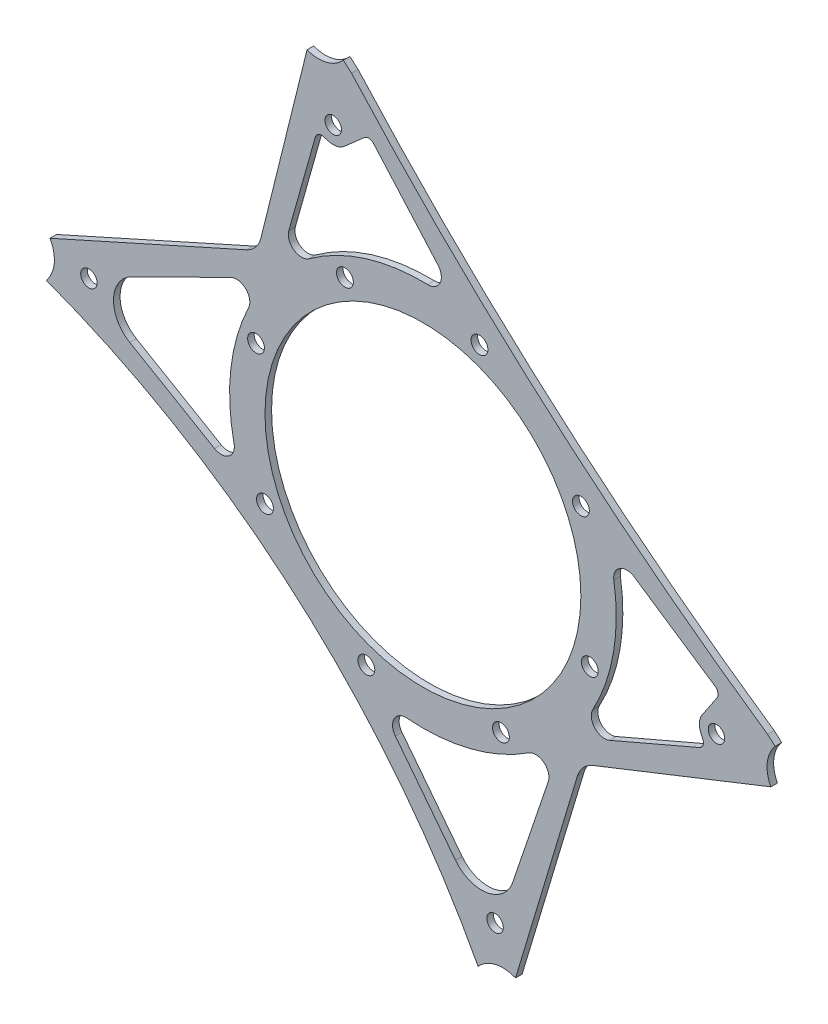
SolidWorks part; units mm, degrees
material "AISI 4130 Steel, normalized at 870C"
ref_plane "Front Plane" through (0, 0, 0) normal (0, 0, 1) x (1, 0, 0)
ref_plane "Top Plane" through (0, 0, 0) normal (0, 1, 0) x (1, 0, 0)
ref_plane "Right Plane" through (0, 0, 0) normal (1, 0, 0) x (0, 0, -1)
sketch "Sketch4" plane through (0, 0, 0) normal (0, 0, 1) x (1, 0, 0)
  line L0 (-176.7423, 45.1325) -> (-186.2949, 53.5013)
  line L1 (-186.2949, 53.5013) -> (-184.2027, 55.8895)
  line L2 (-73.7343, 181.9843) -> (-93.8727, 100.7142)
  line L3 (-184.2027, 55.8895) -> (-99.5727, 93.8894)
  line L4 (1.5645, -106.8565) -> (-0.5277, -109.2446)
  line L5 (-0.5277, -109.2446) -> (-10.0803, -100.8758)
  line L6 (1.5645, -106.8565) -> (28.2602, -18.0689)
  line L7 (112.033, 19.2383) -> (114.1252, 21.6265)
  line L8 (114.1252, 21.6265) -> (101.6402, 32.5643)
  line L9 (-58.9402, 173.2447) -> (-71.6421, 184.3724)
  line L10 (-71.6421, 184.3724) -> (-73.7343, 181.9843)
  line L11 (112.033, 19.2383) -> (34.2509, -11.5474)
  line L12 (-71.6421, 184.3724) -> (114.1252, 21.6265) construction
  line L13 (-0.5277, -109.2446) -> (-285.7287, -247.3934) construction
  line L14 (-71.6421, 184.3724) -> (-186.2949, 53.5013) construction
  line L15 (-186.2949, 53.5013) -> (-0.5277, -109.2446) construction
  line L16 (114.1252, 21.6265) -> (-0.5277, -109.2446) construction
  line L17 (-285.7287, -247.3934) -> (-186.2949, 53.5013) construction
  line L18 (-31.3736, 42.7229) -> (-95.776, 64.5479) construction
  line L19 (-95.776, 64.5479) -> (-63.4526, 179.382) construction
  line L20 (-31.3736, 42.7229) -> (-92.3456, 12.6161) construction
  line L21 (-31.3736, 42.7229) -> (-61.4803, 103.6949) construction
  line L22 (-61.4803, 103.6949) -> (-182.1448, 44.1132) construction
  line L23 (-31.3736, 42.7229) -> (-1.2669, -18.2491) construction
  line L24 (-1.2669, -18.2491) -> (116.7664, 32.5333) construction
  line L25 (-31.3736, 42.7229) -> (33.0288, 20.8978) construction
  line L26 (33.0288, 20.8978) -> (-4.345, -89.3866) construction
  line L27 (-31.3736, 42.7229) -> (-53.1986, -21.6795) construction
  line L28 (-53.1986, -21.6795) -> (-238.3811, 41.0761) construction
  line L29 (-92.3456, 12.6161) -> (-11.5081, -151.0955) construction
  line L30 (-31.3736, 42.7229) -> (29.5984, 72.8296) construction
  line L31 (29.5984, 72.8296) -> (-65.7329, 265.8941) construction
  line L32 (-31.3736, 42.7229) -> (-9.5486, 107.1253) construction
  line L33 (-9.5486, 107.1253) -> (122.2133, 62.4731) construction
  line L34 (-83.1241, 108.5585) -> (-72.9062, 144.8593)
  line L35 (16.9866, -25.6487) -> (3.2858, -66.0777)
  line L36 (40.6971, 0.0819) -> (75.3385, 14.9859)
  line L37 (-105.5123, 81.6695) -> (-143.7132, 62.8066)
  line L38 (-61.3679, 103.4671) -> (-165.6297, 51.9847) construction
  line L39 (-95.5315, 64.4791) -> (-67.9301, 162.5377) construction
  line L40 (-1.3673, -18.0158) -> (92.2723, 22.2715) construction
  line L41 (32.7882, 20.9793) -> (-4.5856, -89.3051) construction
  line L42 (-53.1986, -21.6795) -> (-194.9687, 61.1002) construction
  line L43 (-92.3456, 12.6161) -> (7.9542, -116.6754) construction
  line L44 (-111.7988, 21.3611) -> (-144.4942, 40.452)
  line L45 (-86.3249, 17.2868) -> (13.9749, -112.0047) construction
  line L46 (-49.3564, -15.0992) -> (-187.9967, 65.8531) construction
  line L47 (-42.0345, -39.8057) -> (-18.7768, -69.7861)
  line L48 (29.5984, 72.8296) -> (-58.9402, 173.2447) construction
  line L49 (-9.5486, 107.1253) -> (101.6402, 32.5643) construction
  line L50 (24.8354, 68.63) -> (-63.7032, 169.045) construction
  line L51 (50.1623, 59.4388) -> (81.4099, 38.4847)
  line L52 (-25.528, 125.7491) -> (-50.4102, 153.969)
  line L53 (-13.0852, 101.8513) -> (98.1035, 27.2903) construction
  line L54 (75.8532, 20.2166) -> (76.6679, 18.323)
  line L55 (-61.4803, 103.6949) -> (-165.7422, 52.2125) construction
  line L56 (76.4346, 26.5047) -> (82.1049, 34.9605)
  line L57 (-69.773, 146.6161) -> (-67.7886, 146.0576)
  line L58 (-95.776, 64.5479) -> (-68.1746, 162.6065) construction
  line L59 (-1.2669, -18.2491) -> (92.3727, 22.0382) construction
  line L60 (-61.6317, 147.4611) -> (-53.9952, 154.1943)
  line L61 (93.3291, 30.4919) -> (94.5706, 29.6594)
  line L62 (90.1573, 29.8665) -> (88.3374, 27.1526)
  line L63 (-60.1041, 161.5067) -> (-62.5551, 159.3456)
  line L64 (-68.0318, 162.1763) -> (-67.4152, 164.367)
  line L65 (88.1361, 24.9759) -> (88.8605, 23.2922)
  line L66 (93.9544, 22.9952) -> (91.8639, 22.0958)
  line L67 (-60.8899, 165.8544) -> (-59.9013, 164.7332)
  line L68 (-64.6864, 158.8598) -> (-66.4507, 159.3564)
  line L69 (-65.9993, 152.4145) -> (-70.6731, 153.7301) construction
  line L70 (-65.9993, 152.4145) -> (-55.5471, 161.6406) construction
  line L71 (-53.1986, -21.6795) -> (-191.839, 59.2728) construction
  line L72 (126.1396, 719.3872) -> (-381.4391, -778.4007) construction
  line L73 (-859.7403, -442.1458) -> (679.357, 317.8291) construction
  circle A0 centre (-160.2789, 53.9784) radius 3.175
  circle A1 centre (-3.5293, -83.1085) radius 3.175
  circle A2 centre (81.9195, 22.8266) radius 3.175
  circle A3 centre (-65.9993, 152.4145) radius 3.175
  circle A4 centre (-95.776, 64.5479) radius 3.25
  circle A5 centre (-92.3456, 12.6161) radius 3.25
  circle A6 centre (-53.1986, -21.6795) radius 3.25
  circle A7 centre (-1.2669, -18.2491) radius 3.25
  circle A8 centre (33.0288, 20.8978) radius 3.25
  circle A9 centre (29.5984, 72.8296) radius 3.25
  circle A10 centre (-9.5486, 107.1253) radius 3.25
  circle A11 centre (-61.4803, 103.6949) radius 3.25
  arc A12 (-29.4681, 117.311) -> (-75.247, 103.0731) centre (-31.3736, 42.7229) ccw
  arc A13 (-58.3634, 97.3825) -> (26.3612, 23.1574) centre (-31.3736, 42.7229) ccw
  arc A14 (34.2233, 7.169) -> (42.3158, 54.423) centre (-31.3736, 42.7229) ccw
  arc A15 (-176.7423, 45.1325) -> (-10.0803, -100.8758) centre (-285.7287, -247.3934) cw
  arc A16 (-98.6806, 74.9222) -> (-104.2738, 26.83) centre (-31.3736, 42.7229) ccw
  arc A17 (-58.3634, 97.3825) -> (26.3612, 23.1574) centre (-31.3736, 42.7229) cw
  arc A18 (-104.2738, 26.83) -> (-111.7988, 21.3611) centre (-109.2373, 25.748) cw
  circle A19 centre (-95.776, 64.5479) radius 6 construction
  circle A20 centre (-95.776, 64.5479) radius 3.25 construction
  circle A21 centre (-3.5293, -83.1085) radius 3.175 construction
  circle A22 centre (-31.3736, 42.7229) radius 57 construction
  circle A23 centre (-160.2789, 53.9784) radius 3.175 construction
  circle A24 centre (-31.3736, 42.7229) radius 73.66 construction
  arc A25 (-37.597, -31.6296) -> (9.3994, -19.7638) centre (-31.3736, 42.7229) ccw
  arc A26 (76.4346, 26.5047) -> (75.8532, 20.2166) centre (81.9195, 22.8266) ccw
  arc A27 (-67.7886, 146.0576) -> (-61.6317, 147.4611) centre (-65.9993, 152.4145) ccw
  arc A28 (-37.597, -31.6296) -> (-42.0345, -39.8057) centre (-38.0207, -36.6919) ccw
  arc A29 (-25.528, 125.7491) -> (-29.4681, 117.311) centre (-29.3383, 122.3894) cw
  arc A30 (50.1623, 59.4388) -> (42.3158, 54.423) centre (47.333, 55.2196) ccw
  circle A31 centre (-65.9993, 152.4145) radius 3.175 construction
  arc A32 (40.6971, 0.0819) -> (34.2233, 7.169) centre (38.6894, 4.7483) cw
  circle A33 centre (81.9195, 22.8266) radius 3.175 construction
  arc A34 (-58.9402, 173.2447) -> (101.6402, 32.5643) centre (610.4693, 775.3579) ccw
  arc A35 (16.9866, -25.6487) -> (9.3994, -19.7638) centre (12.1754, -24.0183) ccw
  arc A36 (-98.6806, 74.9222) -> (-105.5123, 81.6695) centre (-103.2632, 77.1145) ccw
  arc A37 (-75.247, 103.0731) -> (-83.1241, 108.5585) centre (-78.2341, 107.1821) cw
  arc A38 (-143.7132, 62.8066) -> (-144.4942, 40.452) centre (-138.0904, 51.4192) ccw
  arc A39 (3.2858, -66.0777) -> (-18.7768, -69.7861) centre (-8.7423, -62.0016) cw
  arc A40 (91.8639, 22.0958) -> (88.8605, 23.2922) centre (90.9604, 24.1957) cw
  arc A41 (82.1049, 34.9605) -> (81.4099, 38.4847) centre (79.9953, 36.3751) ccw
  arc A42 (75.3385, 14.9859) -> (76.6679, 18.323) centre (74.3347, 17.3192) ccw
  arc A43 (34.2509, -11.5474) -> (28.2602, -18.0689) centre (37.99, -20.9944) ccw
  arc A44 (-99.5727, 93.8894) -> (-93.8727, 100.7142) centre (-103.7344, 103.1579) ccw
  circle A45 centre (81.9195, 22.8266) radius 6.604 construction
  circle A46 centre (-65.9993, 152.4145) radius 6.604 construction
  arc A47 (-50.4102, 153.969) -> (-53.9952, 154.1943) centre (-52.3154, 152.2891) ccw
  circle A48 centre (-65.9993, 152.4145) radius 6.604 construction
  arc A49 (88.1361, 24.9759) -> (88.3374, 27.1526) centre (90.236, 25.8794) cw
  arc A50 (-69.773, 146.6161) -> (-72.9062, 144.8593) centre (-70.4612, 144.1711) ccw
  arc A51 (90.1573, 29.8665) -> (93.3291, 30.4919) centre (92.0559, 28.5933) cw
  arc A52 (-59.9013, 164.7332) -> (-60.1041, 161.5067) centre (-61.616, 163.2214) cw
  circle A53 centre (81.9195, 22.8266) radius 6.604 construction
  arc A54 (-62.5551, 159.3456) -> (-64.6864, 158.8598) centre (-64.067, 161.0603) cw
  arc A55 (-66.4507, 159.3564) -> (-68.0318, 162.1763) centre (-65.8313, 161.5569) cw
  arc A56 (93.9544, 22.9952) -> (94.5706, 29.6594) centre (92.4486, 26.495) ccw
  arc A57 (-67.4152, 164.367) -> (-60.8899, 165.8544) centre (-63.7477, 163.3347) cw
  point P115 (-100.5648, 14.8015)
  point P122 (-50.0102, -29.5246)
  point P129 (24.2682, -6.9865)
  point P134 (-89.4016, 89.6246)
  point P175 (-61.6317, 147.4611)
  point P177 (87.6443, 26.119)
  point P188 (-63.4885, 158.5226)
  dimension "D3" = 12
  dimension "D4" = 3.175
  dimension "D2" = 12.7
  dimension "D5" = 60.96
  dimension "D6" = 0.254
  dimension "D8" = 149.225
  dimension "D14" = 5.08
  dimension "D15" = 12.7
  dimension "D16" = 12.7
  dimension "D17" = 2.54
  dimension "D18" = 2.54
  dimension "D19" = 2.54
  dimension "D20" = 10.16
  dimension "D21" = 2.286
  dimension "D22" = 3.81
  dimension "D26" = 9.525
  dimension "D28" = 9.525
  dimension "D13" = 13.208
  dimension "D9" = 7.62
  dimension "D29" = 93
  dimension "D30" = 93
  dimension "D31" = 90
  dimension "D32" = 90
  dimension "D7" = 0.254
  dimension "D10" = 7.62
  dimension "D11" = 6.35
  dimension "D12" = 6.35
extrude "Boss-Extrude1" add sketch "Sketch4" along normal blind 2.54
sketch "Sketch5" plane through (0, 0, 0) normal (0, 0, 1) x (1, 0, 0)
  circle A0 centre (-71.6421, 184.3724) radius 12.7
  circle A1 centre (-186.2949, 53.5013) radius 12.7
  circle A2 centre (-0.5277, -109.2446) radius 12.7
  circle A3 centre (114.1252, 21.6265) radius 12.7
  dimension "D1" = 25.4
extrude "Cut-Extrude1" cut sketch "Sketch5" along normal blind 5.08
extrude "Boss-Extrude2" add sketch "Sketch4<4>" along normal blind 2.54 contours L66 A56 L61 A51 L62 A49 L65 A40 | A57 L64 A55 L68 A54 L63 A52 L67 region at (92.0933, 26.3055, 0) region at (-63.8889, 162.9575, 0)
sketch "Sketch4<4>" plane through (0, 0, 0) normal (0, 0, 1) x (1, 0, 0) same geometry as "Sketch4"
